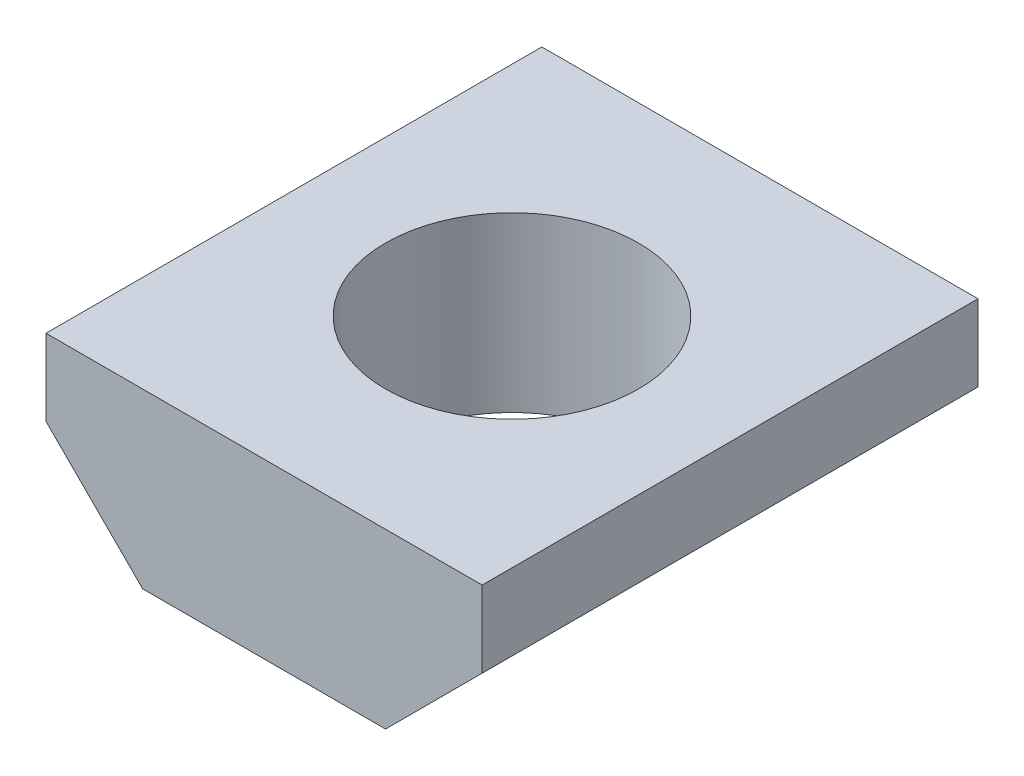
SolidWorks part; units mm, degrees
ref_plane "Front Plane" through (0, 0, 0) normal (0, 0, 1) x (1, 0, 0)
ref_plane "Top Plane" through (0, 0, 0) normal (0, 1, 0) x (1, 0, 0)
ref_plane "Right Plane" through (0, 0, 0) normal (1, 0, 0) x (0, 0, -1)
sketch "Sketch1" plane through (0, 0, 0) normal (0, 0, 1) x (1, 0, 0)
  line L0 (-5.4737, 0) -> (5.4737, 0)
  line L1 (5.4737, 0) -> (5.4737, -1.9177)
  line L2 (5.4737, -1.9177) -> (3.048, -4.3434)
  line L3 (3.048, -4.3434) -> (-3.048, -4.3434)
  line L4 (-3.048, -4.3434) -> (-5.4737, -1.9177)
  line L5 (-5.4737, -1.9177) -> (-5.4737, 0)
  dimension "D1" = 10.9474
  dimension "D2" = 135
  dimension "D3" = 4.3434
  dimension "D4" = 135
  dimension "D5" = 6.096
extrude "Boss-Extrude1" add sketch "Sketch1" along normal blind 12.446
hole_wizard "1/4 (0.25) Diameter Hole1" positions "Sketch2" profile "Sketch3" hole size "1/4" standard "ANSI Inch" end condition through all
sketch "Sketch2" plane through (0, 0, 0) normal (0, 1, 0) x (1, 0, 0)
  point P0 (0, -6.223)
sketch "Sketch3" plane through (0, 0, 6.223) normal (1, 0, 0) x (0, 0, 1)
  line L0 (0, 0) -> (0, 4.3434)
  line L1 (0, 4.3434) -> (3.175, 4.3434)
  line L2 (3.175, 4.3434) -> (3.175, 0)
  line L5 (3.175, 0) -> (0, 0)
  line L11 (0, -6.35) -> (0, 107.95) construction
  dimension "Thru Hole Dia." = 6.35
  dimension "Thru Hole Depth" = 4.3434
